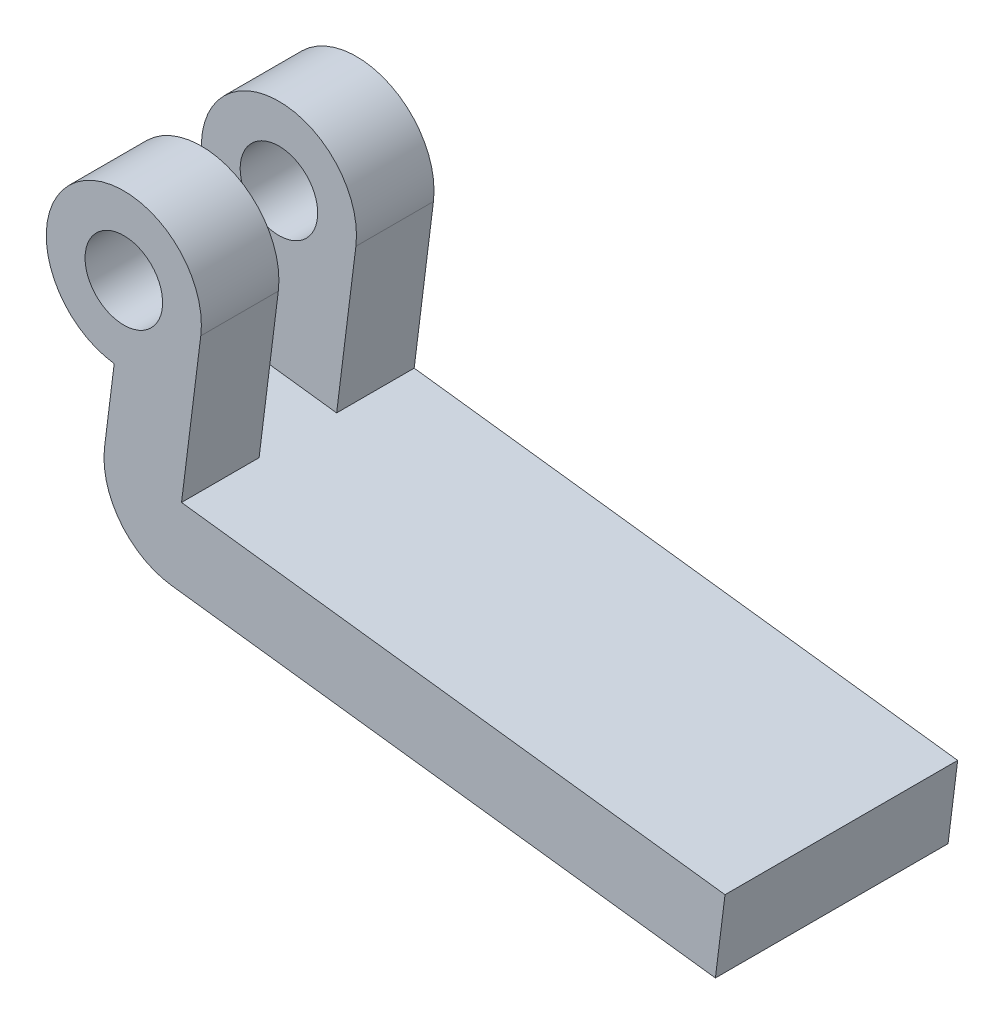
SolidWorks part; units mm, degrees
ref_plane "Front Plane" through (0, 0, 0) normal (0, 0, 1) x (1, 0, 0)
ref_plane "Top Plane" through (0, 0, 0) normal (0, 1, 0) x (1, 0, 0)
ref_plane "Right Plane" through (0, 0, 0) normal (1, 0, 0) x (0, 0, -1)
sketch "Sketch1" plane through (0, 0, 0) normal (0, 0, 1) x (1, 0, 0)
  line L1 (50.8, -6.35) -> (6.301, -0.7876) construction
  line L2 (50.8, -6.35) -> (50.0124, -12.651) construction
  line L3 (50.0124, -12.651) -> (-0.7876, -6.301) construction
  line L4 (6.301, -0.7876) -> (4.7257, -13.3895)
  line L5 (4.7257, -13.3895) -> (49.2248, -18.9519)
  line L6 (49.2248, -18.9519) -> (48.4371, -25.2529)
  line L7 (48.4371, -25.2529) -> (-2.3629, -18.9029)
  line L8 (-2.3629, -18.9029) -> (-0.7876, -6.301)
  circle A0 centre (0, 0) radius 3.175
  arc A1 (6.301, -0.7876) -> (-0.7876, -6.301) centre (0, 0) ccw
  point P3 (0, 0)
  point P12 (0, 0)
  dimension "D1" = 6.35
  dimension "D2" = 12.7
  dimension "D3" = 50.8
  dimension "D4" = 12.7
  dimension "D5" = 6.35
  dimension "D6" = 50.8
extrude "Boss-Extrude1" add sketch "Sketch1" along normal mid plane 19.05
sketch "Sketch2" plane through (0, 0, 9.525) normal (0, 0, 1) x (1, 0, 0)
  line L4 (49.2248, -18.9519) -> (-15.7645, -10.8283)
  line L5 (48.4371, -25.2529) -> (49.2248, -18.9519) construction
  line L6 (49.2248, -18.9519) -> (4.7257, -13.3895) construction
  line L7 (-15.7645, -10.8283) -> (-12.9598, 11.6095)
  line L8 (-12.9598, 11.6095) -> (52.0295, 3.4858)
  line L9 (52.0295, 3.4858) -> (49.2248, -18.9519)
extrude "Cut-Extrude1" cut sketch "Sketch2" against normal blind 6.35 from offset 6.35 offset against normal yes
fillet "Fillet1" radius 6.35 1 edges at (-2.3629, -18.9029, 0)
equation "\"`\"=1.60553"
